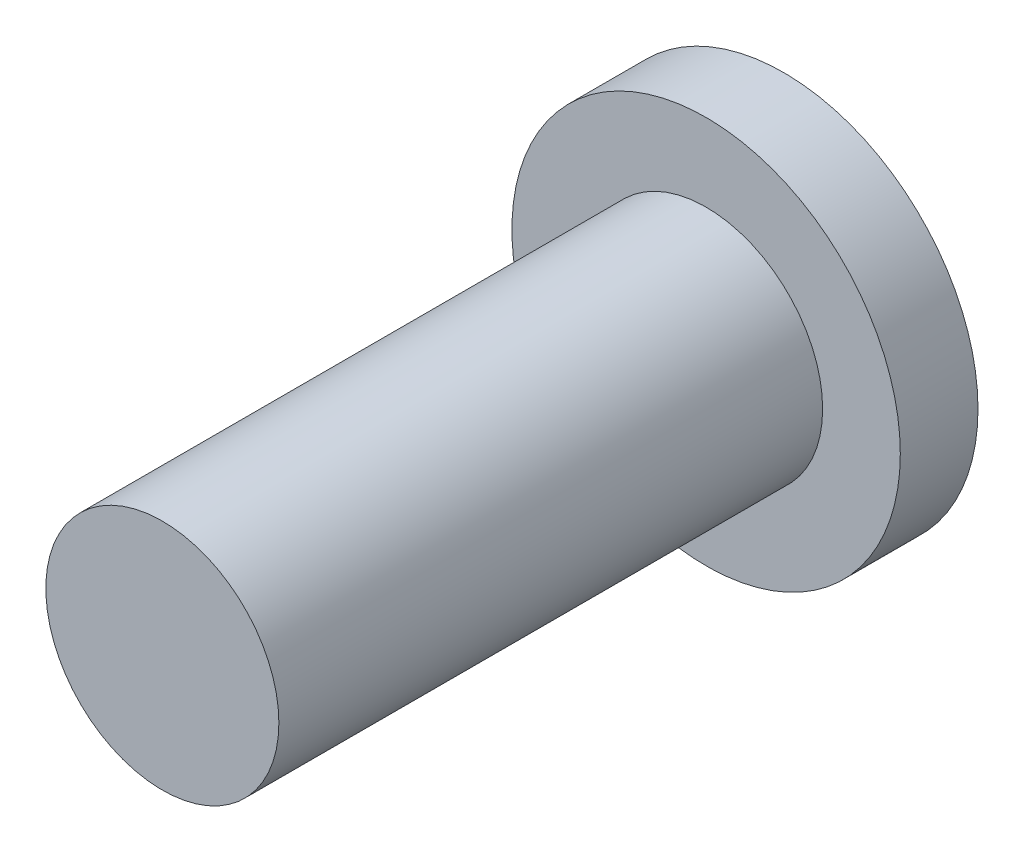
SolidWorks part; units mm, degrees
ref_plane "Front Plane" through (0, 0, 0) normal (0, 0, 1) x (1, 0, 0)
ref_plane "Top Plane" through (0, 0, 0) normal (0, 1, 0) x (1, 0, 0)
ref_plane "Right Plane" through (0, 0, 0) normal (1, 0, 0) x (0, 0, -1)
sketch "Sketch1" plane through (0, 0, 0) normal (0, 0, 1) x (1, 0, 0)
  circle A0 centre (0, 0) radius 7.5
  circle A1 centre (0, 0) radius 12.5
  dimension "D1" = 15
  dimension "D2" = 25
extrude "Boss-Extrude1" add sketch "Sketch1" along normal blind 5
extrude "Boss-Extrude2" add sketch "Sketch1<2>" along normal blind 40 contours A0 region at (0, 0, 0)
sketch "Sketch1<2>" plane through (0, 0, 0) normal (0, 0, 1) x (1, 0, 0) same geometry as "Sketch1"
